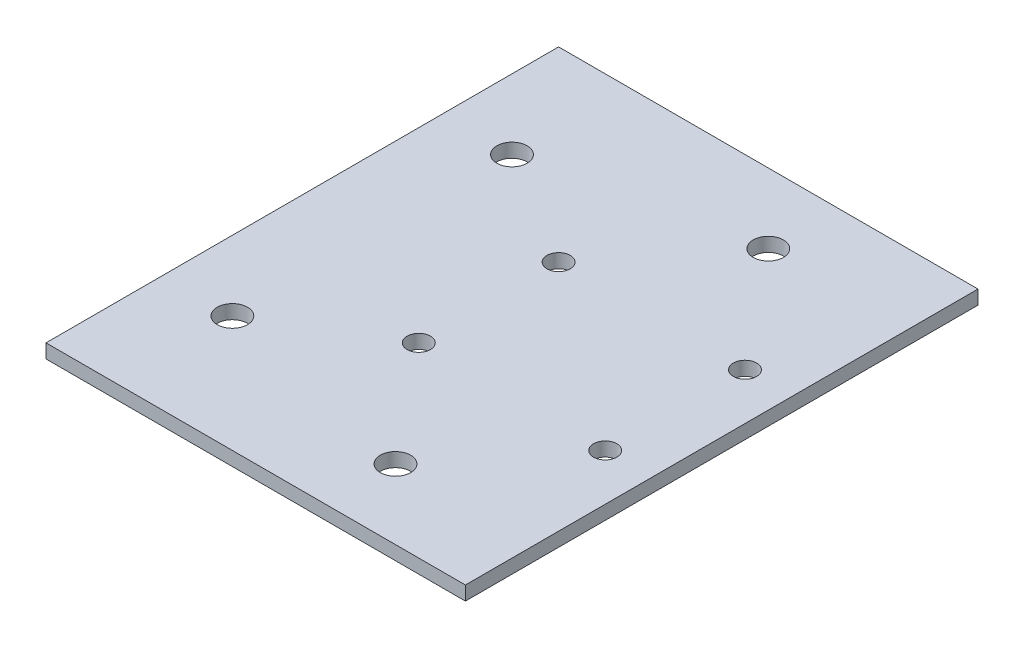
SolidWorks part; units mm, degrees
material "1023 Carbon Steel Sheet (SS)"
ref_plane "Front Plane" through (0, 0, 0) normal (0, 0, 1) x (1, 0, 0)
ref_plane "Top Plane" through (0, 0, 0) normal (0, 1, 0) x (1, 0, 0)
ref_plane "Right Plane" through (0, 0, 0) normal (1, 0, 0) x (0, 0, -1)
sketch "Sketch1" plane through (0, 0, 0) normal (0, 1, 0) x (1, 0, 0)
  line L0 (-15, 55) -> (-15, -55) construction
  line L1 (-45, 55) -> (45, 55)
  line L2 (-45, 55) -> (-45, -55)
  line L3 (-45, -55) -> (45, -55)
  line L4 (45, 55) -> (45, -55)
  line L5 (-45, 55) -> (45, -55) construction
  line L6 (-45, -55) -> (45, 55) construction
  line L7 (-5, 15) -> (35, 15) construction
  line L8 (-5, 15) -> (-5, -15) construction
  line L9 (-5, -15) -> (35, -15) construction
  line L10 (35, 15) -> (35, -15) construction
  line L11 (-5, 15) -> (35, -15) construction
  line L12 (-5, -15) -> (35, 15) construction
  circle A0 centre (-30, 30) radius 3.25
  circle A1 centre (-30, -30) radius 3.25
  circle A2 centre (-5, 15) radius 2.5
  circle A3 centre (35, 15) radius 2.5
  circle A4 centre (35, -15) radius 2.5
  circle A5 centre (-5, -15) radius 2.5
  circle A6 centre (15, -40) radius 3.25
  circle A7 centre (15, 40) radius 3.25
  point P0 (0, 0)
  point P11 (15, 0)
  dimension "D3" = 6.5
  dimension "D11" = 5
  dimension "D12" = 15
  dimension "D14" = 6.5
  dimension "D1" = 110
  dimension "D2" = 90
  dimension "D4" = 15
  dimension "D5" = 60
  dimension "D6" = 30
  dimension "D7" = 30
  dimension "D8" = 40
  dimension "D9" = 30
  dimension "D10" = 30
  dimension "D13" = 30
  dimension "D15" = 15
extrude "Boss-Extrude1" add sketch "Sketch1" along normal blind 3
